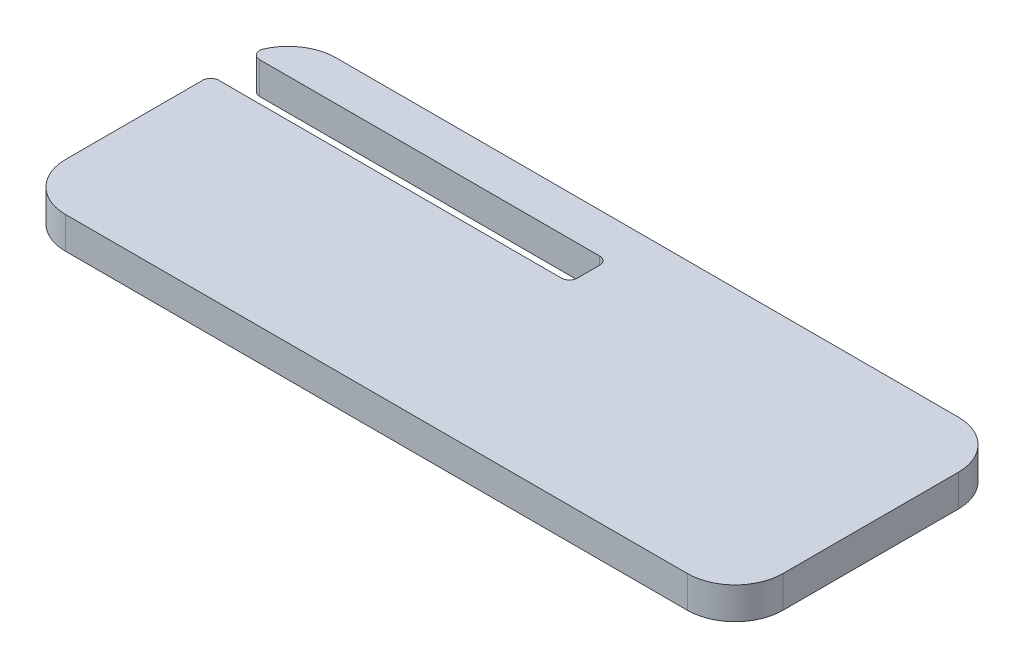
SolidWorks part; units mm, degrees
ref_plane "Alzado" through (0, 0, 0) normal (0, 0, 1) x (1, 0, 0)
ref_plane "Planta" through (0, 0, 0) normal (0, 1, 0) x (1, 0, 0)
ref_plane "Vista lateral" through (0, 0, 0) normal (1, 0, 0) x (0, 0, -1)
sketch "Croquis1" plane through (0, 0, 0) normal (0, 1, 0) x (1, 0, 0)
  line L5 (-22.5, 9.9298) -> (22.5, 9.9298)
  line L6 (-22.5, 9.9298) -> (-22.5, -7.0702)
  line L7 (-22.5, -7.0702) -> (22.5, -7.0702)
  line L8 (22.5, 9.9298) -> (22.5, -7.0702)
  dimension "D1" = 9.9298
  dimension "D2" = 22.5
  dimension "D3" = 17
  dimension "D4" = 45
extrude "Saliente-Extruir1" add sketch "Croquis1" along normal blind 2
sketch "Croquis2" plane through (0, 2, 0) normal (0, 1, 0) x (1, 0, 0)
  line L0 (-22.5, 9.9298) -> (-22.5, -7.0702) construction
  line L1 (-22.5, 7.4298) -> (0, 7.4298)
  line L2 (-22.5, 7.4298) -> (-22.5, 5.0298)
  line L3 (-22.5, 5.0298) -> (0, 5.0298)
  line L4 (0, 7.4298) -> (0, 5.0298)
  line L6 (22.5, 9.9298) -> (-22.5, 9.9298) construction
  dimension "D1" = 22.5
  dimension "D2" = 2.5
  dimension "D3" = 2.4
extrude "Cortar-Extruir1" cut sketch "Croquis2" against normal up to surface (2 mm away) up to face at (0, 0, -1.4298)
fillet "Redondeo1" radius 3 4 edges at (-22.5, 1, 7.0702) (-22.5, 1, -9.9298) (22.5, 1, 7.0702) (22.5, 1, -9.9298)
fillet "Redondeo4" radius 0.5 4 edges at (-22.5, 1, -5.0298) (0, 1, -5.0298) (0, 1, -7.4298) (-22.5, 1, -7.4298)
